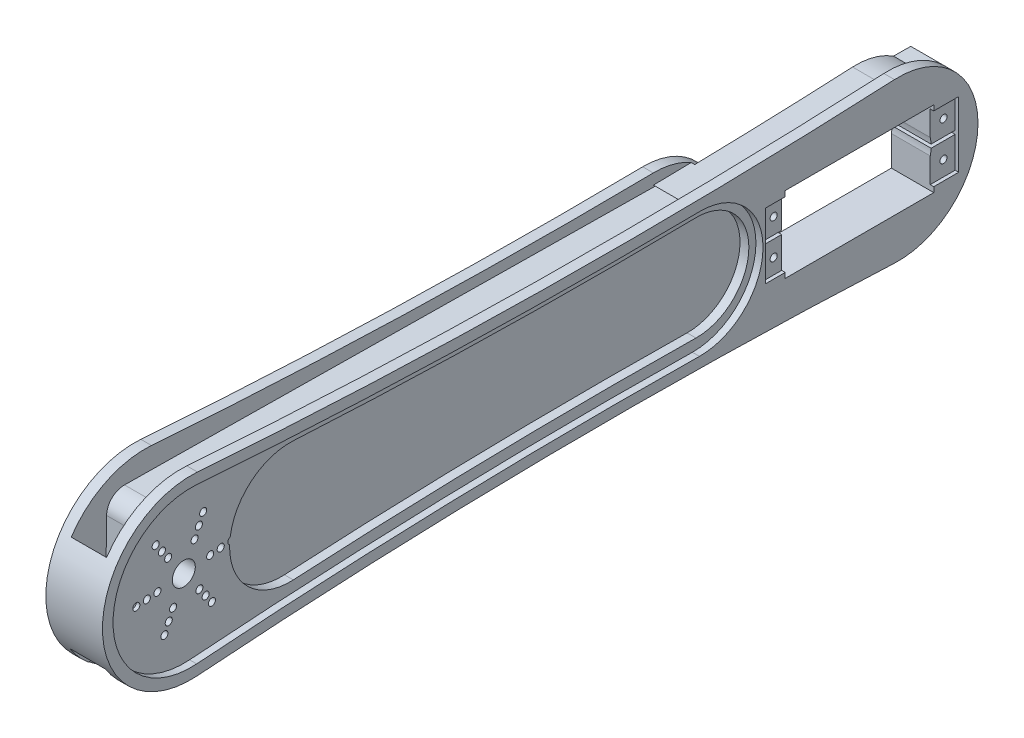
SolidWorks part; units mm, degrees
ref_plane "Front Plane" through (0, 0, 0) normal (0, 0, 1) x (1, 0, 0)
ref_plane "Top Plane" through (0, 0, 0) normal (0, 1, 0) x (1, 0, 0)
ref_plane "Right Plane" through (0, 0, 0) normal (1, 0, 0) x (0, 0, -1)
sketch "Sketch1" plane through (0, 0, 0) normal (1, 0, 0) x (0, 0, -1)
  line L0 (0, 0) -> (200, 0) construction
  line L1 (-25, 0) -> (0, 0) construction
  line L2 (0, -25) -> (0, 25) construction
  line L3 (100, -19.4143) -> (100, 19.4143) construction
  line L4 (225, 0) -> (200, 0) construction
  arc A0 (1.8507, 24.9314) -> (1.8507, -24.9314) centre (0, 0) ccw
  arc A1 (198.8947, -22.4728) -> (198.8947, 22.4728) centre (200, 0) ccw
  circle A2 centre (0, 0) radius 3.25
  circle A6 centre (200, 0) radius 3.25
  arc A8 (1.8507, 24.9314) -> (198.8947, 22.4728) centre (120.2969, 1620.5412) ccw
  arc A9 (1.8507, -24.9314) -> (198.8947, -22.4728) centre (120.2969, -1620.5412) cw
  circle A11 centre (0, 0) radius 7.25 construction
  point P12 (0, 0)
  point P17 (100, 0)
  dimension "D2" = 50
  dimension "D3" = 45
  dimension "D4" = 6.5
  dimension "D8" = 1600
  dimension "D1" = 200
extrude "Boss-Extrude1" add sketch "Sketch1" along normal blind 16
sketch "Sketch3" plane through (16, 0, 0) normal (1, 0, 0) x (0, 0, -1)
  arc A0 (1.4065, 18.9479) -> (199.1895, 16.4801) centre (120.2969, 1620.5412) ccw
  arc A1 (199.1895, -16.4801) -> (1.4065, -18.9479) centre (120.2969, -1620.5412) ccw
  arc A2 (30.9488, 17.0285) -> (30.9488, -17.0285) centre (30, 0) ccw
  arc A3 (144.7755, 14.7277) -> (144.7755, -14.7277) centre (145, 0) cw
  arc A14 (199.0421, -19.4765) -> (199.0421, 19.4765) centre (200, 0) ccw
  arc A15 (199.0421, -19.4765) -> (1.6286, -21.9396) centre (120.2969, -1620.5412) ccw
  arc A16 (1.6286, 21.9396) -> (1.6286, -21.9396) centre (0, 0) ccw
  arc A17 (1.6286, 21.9396) -> (199.0421, 19.4765) centre (120.2969, 1620.5412) ccw
  arc A18 (199.0421, -19.4765) -> (199.0421, 19.4765) centre (200, 0) ccw
  arc A19 (199.0421, -19.4765) -> (1.6286, -21.9396) centre (120.2969, -1620.5412) ccw
  arc A20 (1.6286, 21.9396) -> (1.6286, -21.9396) centre (0, 0) ccw
  arc A21 (1.6286, 21.9396) -> (199.0421, 19.4765) centre (120.2969, 1620.5412) ccw
  circle M5 centre (200, 0) radius 3.25
  circle M7 centre (0, 0) radius 3.25
  dimension "D4" = 55
  dimension "D3" = 30
  dimension "D1" = 3
  dimension "D2" = 3
extrude "Cut-Extrude1" cut sketch "Sketch3" against normal blind 2 contours A21 A20 A19 A18 A3 A1 A2 A0 M5 M7 region at (16, -15.2114, -100.2668)
extrude "Cut-Extrude3" cut sketch "Sketch3<2>" along normal blind 1.5 from offset 16 contours A21 A20 A19 A18 A3 A1 A2 A0 M5 M7 region at (16, -15.2114, -100.2668) offset against normal yes
sketch "Sketch3<2>" plane through (16, 0, 0) normal (1, 0, 0) x (0, 0, -1) same geometry as "Sketch3"
sketch "Sketch7" plane through (16, 0, 0) normal (1, 0, 0) x (0, 0, -1)
  line L0 (30.7819, 14.0331) -> (57.579, -12.764) construction
  line L1 (57.579, -12.764) -> (20.4511, -12.764) construction
  circle A8 centre (30.7819, 14.0331) radius 1.5
  arc A9 (30.7819, 14.0331) -> (144.8212, 11.7281) centre (120.2969, 1620.5412) ccw
  arc A10 (30.7819, 14.0331) -> (191.7926, 13.1304) centre (120.2969, 1620.5412) ccw construction
  arc A13 (144.8212, -11.7281) -> (30.7819, -14.0331) centre (120.2969, -1620.5412) ccw
  arc A14 (193.3857, -13.2021) -> (30.7819, -14.0331) centre (120.2969, -1620.5412) ccw construction
  dimension "D2" = 3
  dimension "D4" = 45
  dimension "D1" = 3
  dimension "D3" = 3
ref_plane "Plane1" through (0, 24.998, -0.3125) normal (0, 0.9999, -0.0125) x (1, 0, 0)
sketch "Sketch15" plane through (0, 24.998, -0.3125) normal (0, 0.9999, -0.0125) x (1, 0, 0)
  line L0 (8, 198.5983) -> (8, 1.5389) construction
  line L1 (16, 198.5983) -> (0, 198.5983) construction
  line L2 (16, 1.5389) -> (0, 1.5389) construction
  line L3 (3, 198.5983) -> (3, 1.5389)
  line L4 (13, 198.5983) -> (13, 1.5389)
  line L5 (3, 198.5983) -> (13, 198.5983)
  line L6 (3, 1.5389) -> (13, 1.5389)
  dimension "D1" = 5
  dimension "D2" = 5
extrude "Cut-Extrude9" cut sketch "Sketch15" against normal blind 6
sketch "Sketch16" plane through (0, -2.4825, -198.5828) normal (0, 0.0125, 0.9999) x (1, 0, 0)
  line L0 (3, 24.9573) -> (3, 27.0919)
  line L1 (3, 27.0919) -> (13, 27.0919)
  line L2 (13, 27.0919) -> (13, 24.9573)
  line L4 (3, 24.9573) -> (3, 19)
  line L5 (3, 19) -> (13, 19)
  line L6 (13, 19) -> (13, 24.9573)
  line L7 (13, 24.9573) -> (3, 24.9573)
  line L8 (3, 24.9573) -> (3, 19)
  line L9 (3, 19) -> (13, 19)
  line L10 (13, 19) -> (13, 24.9573)
  dimension "D1" = 0
extrude "Cut-Extrude10" cut sketch "Sketch16" against normal through all both and the other way through all
sketch "Sketch17" plane through (0, 18.9985, -0.2375) normal (0, 0.9999, -0.0125) x (1, 0, 0)
  line L0 (3, -11) -> (13, -11)
  line L1 (3, -11) -> (3, -21)
  line L2 (13, -11) -> (13, -21)
  line L3 (3, -21) -> (13, -21)
  line L4 (3, 215.2814) -> (3, -16.2481) construction
  line L5 (13, 1.5389) -> (13, -16.2481) construction
  dimension "D1" = 10
  dimension "D2" = 4
extrude "Cut-Extrude11" cut sketch "Sketch17" against normal through all
fillet "Fillet8" radius 5 2 edges at (8, -22.3107, 11.2798) (8, 19.136, 10.7616)
sketch "Sketch18" plane through (16, 0, 0) normal (1, 0, 0) x (0, 0, -1)
  arc A0 (143.7555, 17.7128) -> (143.7555, -17.7128) centre (144.0147, 0) cw
  arc A1 (1.6286, 21.9396) -> (199.0421, 19.4765) centre (120.2969, 1620.5412) ccw construction
  arc A2 (199.0421, -19.4765) -> (1.6286, -21.9396) centre (120.2969, -1620.5412) ccw construction
  arc A3 (1.6286, 21.9396) -> (199.0421, 19.4765) centre (120.2969, 1620.5412) ccw construction
  arc A4 (199.0421, -19.4765) -> (199.0421, 19.4765) centre (200, 0) ccw construction
  arc A5 (199.0421, -19.4765) -> (143.7555, -17.7128) centre (120.2969, -1620.5412) ccw
  arc A6 (143.7555, 17.7128) -> (199.0421, 19.4765) centre (120.2969, 1620.5412) ccw
  arc A7 (199.0421, -19.4765) -> (199.0421, 19.4765) centre (200, 0) ccw
  arc A8 (144.7755, -14.7277) -> (144.7755, 14.7277) centre (145, 0) ccw construction
  point P16 (159.7294, 0)
  point P17 (161.7294, 0)
  dimension "D1" = 2
extrude "Boss-Extrude2" add sketch "Sketch18" against normal up to surface (16 mm away) up to face at (0, 0, -99.5237)
sketch "Sketch21" plane through (16, 0, 0) normal (1, 0, 0) x (0, 0, -1)
  line L0 (222.5, 0) -> (-25, 0) construction
  line L1 (168, -10.75) -> (210, -10.75)
  line L2 (168, -10.75) -> (168, -0.5)
  line L3 (210, -10.75) -> (210, -2.25)
  line L4 (168, 10.75) -> (210, 10.75)
  line L5 (168, -10.75) -> (210, 10.75) construction
  line L6 (168, 10.75) -> (210, -10.75) construction
  line L7 (210, -10.75) -> (210.2846, -10.7404) construction
  line L8 (162.45, -0.5) -> (162.45, 0.5) construction
  line L9 (162.45, 0.5) -> (169.25, 0.5) construction
  line L11 (169.25, -0.5) -> (162.45, -0.5) construction
  line L12 (217.05, -0.5) -> (210.25, -0.5) construction
  line L13 (168, 0.5) -> (168, 10.75)
  line L14 (210.25, 0.5) -> (217.05, 0.5) construction
  line L15 (217.05, 0.5) -> (217.05, -0.5) construction
  line L16 (162.45, -0.5) -> (162.45, 0.5)
  line L17 (162.45, 0.5) -> (168, 0.5)
  line L19 (168, -0.5) -> (162.45, -0.5)
  line L20 (217.05, -0.5) -> (210.25, -0.5)
  line L22 (210.25, 0.5) -> (217.05, 0.5)
  line L23 (217.05, 0.5) -> (217.05, -0.5)
  line L24 (210, 2.25) -> (210, 10.75)
  line L25 (210.25, -0.5) -> (210.2378, -0.5)
  line L27 (210.2378, 0.5) -> (210.25, 0.5)
  arc A0 (198.8947, -22.4728) -> (198.8947, 22.4728) centre (200, 0) ccw construction
  arc A1 (1.8507, 24.9314) -> (1.8507, -24.9314) centre (0, 0) ccw construction
  arc A3 (210.2378, 0.5) -> (210, 2.25) centre (200, 0) ccw
  arc A4 (210, -2.25) -> (210.2378, -0.5) centre (200, 0) ccw
  point P30 (189, 0)
  dimension "D1" = 42
  dimension "D2" = 21.5
  dimension "D3" = 12.5
  dimension "D4" = 33.5
extrude "Cut-Extrude13" cut sketch "Sketch21" against normal blind 12
sketch "Sketch23" plane through (0, 0, 0) normal (-1, 0, 0) x (0, 0, 1)
  arc A4 (-144.7755, 14.7277) -> (-144.7755, -14.7277) centre (-145, 0) ccw
  arc A5 (-144.7755, 14.7277) -> (-144.7755, -14.7277) centre (-145, 0) ccw
  arc A6 (-30.9488, -17.0285) -> (-144.7755, -14.7277) centre (-120.2969, -1620.5412) ccw
  arc A7 (-30.9488, -17.0285) -> (-144.7755, -14.7277) centre (-120.2969, -1620.5412) ccw
  arc A8 (-30.9488, -17.0285) -> (-30.9488, 17.0285) centre (-30, 0) ccw
  arc A9 (-30.9488, -17.0285) -> (-30.9488, 17.0285) centre (-30, 0) ccw
  arc A10 (-144.7755, 14.7277) -> (-30.9488, 17.0285) centre (-120.2969, 1620.5412) ccw
  arc A11 (-144.7755, 14.7277) -> (-30.9488, 17.0285) centre (-120.2969, 1620.5412) ccw
  dimension "D1" = 0
extrude "Cut-Extrude15" cut sketch "Sketch23" against normal blind 4.5
sketch "Sketch24" plane through (16, 0, 0) normal (1, 0, 0) x (0, 0, -1)
  arc A4 (144.7755, -14.7277) -> (144.7755, 14.7277) centre (145, 0) ccw
  arc A5 (144.7755, -14.7277) -> (144.7755, 14.7277) centre (145, 0) ccw
  arc A6 (30.9488, 17.0285) -> (144.7755, 14.7277) centre (120.2969, 1620.5412) ccw
  arc A7 (30.9488, 17.0285) -> (144.7755, 14.7277) centre (120.2969, 1620.5412) ccw
  arc A8 (30.9488, 17.0285) -> (30.9488, -17.0285) centre (30, 0) ccw
  arc A9 (30.9488, 17.0285) -> (30.9488, -17.0285) centre (30, 0) ccw
  arc A10 (144.7755, -14.7277) -> (30.9488, -17.0285) centre (120.2969, -1620.5412) ccw
  arc A11 (144.7755, -14.7277) -> (30.9488, -17.0285) centre (120.2969, -1620.5412) ccw
  dimension "D1" = 0
extrude "Cut-Extrude16" cut sketch "Sketch24" against normal blind 4.5
sketch "Sketch26" plane through (16, 0, 0) normal (1, 0, 0) x (0, 0, -1)
  line L0 (162.45, 0.5) -> (162.45, 3.75) construction
  line L1 (163.45, 9.25) -> (169.25, 9.25) construction
  line L2 (210.25, 9.25) -> (216.05, 9.25) construction
  line L4 (162.45, 0.5) -> (162.45, 3.75)
  line L5 (163.45, 9.25) -> (169.25, 9.25)
  line L6 (210.25, 9.25) -> (216.05, 9.25)
  line L8 (163.45, -9.25) -> (169.25, -9.25) construction
  line L9 (210.25, -9.25) -> (216.05, -9.25) construction
  line L10 (163.45, -9.25) -> (169.25, -9.25)
  line L11 (210.25, -9.25) -> (216.05, -9.25)
  line L12 (162.45, -9.2872) -> (162.45, 9.25)
  line L13 (162.45, 9.25) -> (217.05, 9.25)
  line L14 (162.45, 9.25) -> (162.45, -9.2872)
  line L15 (217.05, 9.25) -> (217.05, -9.2872)
  line L16 (162.45, -9.2872) -> (217.05, -9.2872)
  arc A0 (215.4375, -3.75) -> (215.4375, -6.25) centre (213.75, -5) ccw construction
  arc A1 (215.4375, 6.25) -> (215.4375, 3.75) centre (213.75, 5) ccw construction
  arc A2 (164.0625, -6.25) -> (164.0625, -3.75) centre (165.75, -5) ccw construction
  arc A3 (164.0625, 3.75) -> (164.0625, 6.25) centre (165.75, 5) ccw construction
  arc A4 (215.4375, -3.75) -> (215.4375, -6.25) centre (213.75, -5) ccw
  arc A5 (215.4375, 6.25) -> (215.4375, 3.75) centre (213.75, 5) ccw
  arc A6 (164.0625, -6.25) -> (164.0625, -3.75) centre (165.75, -5) ccw
  arc A7 (164.0625, 3.75) -> (164.0625, 6.25) centre (165.75, 5) ccw
  circle A8 centre (165.75, 5) radius 1
  circle A9 centre (165.75, -5) radius 1
  circle A10 centre (213.75, -5) radius 1
  circle A11 centre (213.75, 5) radius 1
  point P27 (162.45, 2.125)
  dimension "D1" = 2
extrude "Cut-Extrude17" cut sketch "Sketch26" against normal blind 6 contours A11 | A10 | A9 | A8 region at (16, 5, -165.75) region at (16, -5, -165.75) region at (16, -5, -213.75) region at (16, 5, -213.75)
extrude "Cut-Extrude18" cut sketch "Sketch26<3>" against normal blind 1 and the other way through all contours L13 L12 L4 L5 A8 | L12 L16 A9 | L16 L15 A10 | L15 L13 L6 A11 region at (16, 2.125, -162.5536) region at (16, -0.6039, -165.225) region at (16, -5.7686, -210.1127) region at (16, 9.1376, -210.125)
sketch "Sketch26<3>" plane through (16, 0, 0) normal (1, 0, 0) x (0, 0, -1) same geometry as "Sketch26"
sketch "Sketch28" plane through (0, 0, 0) normal (-1, 0, 0) x (0, 0, 1)
  arc A1 (-1.8507, -24.9314) -> (-198.8947, -22.4728) centre (-120.2969, -1620.5412) ccw construction
  arc A2 (-143.7116, 20.7125) -> (-143.7116, -20.7125) centre (-144.0147, 0) ccw
  arc A3 (-143.7116, 20.7125) -> (-143.7116, -20.7125) centre (-144.0147, 0) ccw
  arc A4 (-198.8947, 22.4728) -> (-198.8947, -22.4728) centre (-200, 0) ccw construction
  arc A5 (-198.8947, 22.4728) -> (-1.8507, 24.9314) centre (-120.2969, 1620.5412) ccw construction
  arc A6 (-143.7116, -20.7125) -> (-198.8947, -22.4728) centre (-120.2969, -1620.5412) ccw
  arc A7 (-198.8947, 22.4728) -> (-198.8947, -22.4728) centre (-200, 0) ccw
  arc A8 (-198.8947, 22.4728) -> (-143.7116, 20.7125) centre (-120.2969, 1620.5412) ccw
  dimension "D1" = 3
extrude "Cut-Extrude19" cut sketch "Sketch28" against normal blind 4
ref_plane "Plane2" through (0, 0, 0) normal (0, 1, 0) x (1, 0, 0)
mirror "Mirror1" about plane through (0, 0, 0) normal (0, 1, 0) of "Cut-Extrude9"
sketch "Sketch29" plane through (0, 0.0192, -1.5388) normal (0, 0.0125, -0.9999) x (-1, 0, 0)
  line L0 (-3, -19) -> (-2.5, -19)
  line L1 (-13, -19) -> (-13.5, -19)
  line L3 (-3, -27.2305) -> (-13, -27.2305)
  line L4 (-13, -24.9526) -> (-3, -24.9526)
  line L5 (-3, -24.9526) -> (-3, -19)
  line L6 (-3, -19) -> (-13, -19)
  line L7 (-13, -19) -> (-13, -24.9526)
  line L8 (-13, -24.9526) -> (-3, -24.9526)
  line L10 (-3, -19) -> (-13, -19)
  line L12 (-3, -27.2305) -> (-2.5, -27.2305)
  line L13 (-2.5, -27.2305) -> (-2.5, -19)
  line L14 (-8, -19) -> (-8, -27.2305) construction
  line L15 (-13.5, -27.2305) -> (-13.5, -19)
  line L16 (-13, -27.2305) -> (-13.5, -27.2305)
  line M5 (-13, -24.9526) -> (-3, -24.9526)
  line M6 (-3, -24.9526) -> (-3, -19)
  line M7 (-3, -19) -> (-13, -19)
  line M8 (-13, -19) -> (-13, -24.9526)
  dimension "D2" = 0.5
  dimension "D1" = 0
extrude "Cut-Extrude20" cut sketch "Sketch29" against normal through all both and the other way through all contours L14 L10 M8 M5 | L14 L8 M7 M6 | L14 L1 L15 L16 L3 M5 M8 | L8 L14 L3 L12 L13 L0 M6 region at (4.7701, -25.2804, -1.8551) region at (5.5, -21.9553, -1.8135) region at (10.5, -21.9553, -1.8135) region at (11.2299, -25.2804, -1.8551)
fillet "Fillet9" radius 5 1 edges at (8, -19.1419, 11.2361)
sketch "Sketch32" plane through (14, 0, 0) normal (1, 0, 0) x (0, 0, -1)
  line L0 (0, 0) -> (5.4763, 12.3394) construction
  circle A0 centre (0, 0) radius 10.5 construction
  circle A1 centre (0, 0) radius 13.5 construction
  circle A2 centre (0, 0) radius 7.5 construction
  circle A3 centre (3.0424, 6.8552) radius 1
  circle A4 centre (4.2593, 9.5973) radius 1
  circle A5 centre (5.4763, 12.3394) radius 1
  circle A6 centre (13.4244, 1.4271) radius 1
  circle A7 centre (10.4412, 1.1099) radius 1
  circle A8 centre (7.458, 0.7928) radius 1
  circle A9 centre (7.9481, -10.9123) radius 1
  circle A10 centre (6.1818, -8.4873) radius 1
  circle A11 centre (4.4156, -6.0624) radius 1
  circle A12 centre (-5.4763, -12.3394) radius 1
  circle A13 centre (-4.2593, -9.5973) radius 1
  circle A14 centre (-3.0424, -6.8552) radius 1
  circle A15 centre (-13.4244, -1.4271) radius 1
  circle A16 centre (-10.4412, -1.1099) radius 1
  circle A17 centre (-7.458, -0.7928) radius 1
  circle A18 centre (-7.9481, 10.9123) radius 1
  circle A19 centre (-6.1818, 8.4873) radius 1
  circle A20 centre (-4.4156, 6.0624) radius 1
  point P44 (0, 0)
  dimension "D1" = 6
extrude "Cut-Extrude21" cut sketch "Sketch32" against normal blind 6
